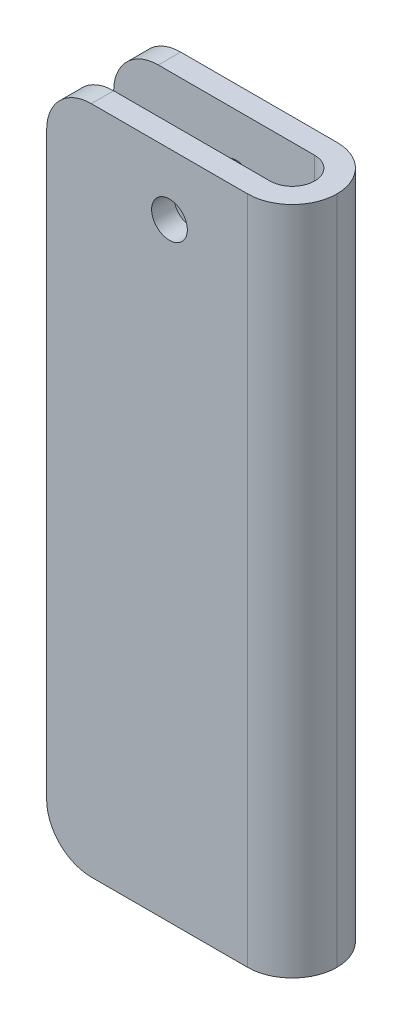
SolidWorks part; units mm, degrees
ref_plane "Plan de face" through (0, 0, 0) normal (0, 0, 1) x (1, 0, 0)
ref_plane "Plan de dessus" through (0, 0, 0) normal (0, 1, 0) x (1, 0, 0)
ref_plane "Plan de droite" through (0, 0, 0) normal (1, 0, 0) x (0, 0, -1)
sketch "Esquisse1" plane through (0, 0, 0) normal (0, 0, 1) x (1, 0, 0)
  line L1 (0, 0) -> (-55, 0)
  line L2 (0, 0) -> (0, 150)
  line L3 (0, 150) -> (-55, 150)
  line L4 (-55, 0) -> (-55, 150)
  dimension "D1" = 55
  dimension "D2" = 150
extrude "Boss.-Extru.1" add sketch "Esquisse1" along normal blind 20
sketch "Esquisse2" plane through (0, 150, 0) normal (0, 1, 0) x (1, 0, 0)
  line L0 (-55, -20) -> (-55, 0) construction
  line L1 (-55, -5) -> (-5, -5)
  line L2 (-55, -5) -> (-55, -15)
  line L3 (-55, -15) -> (-5, -15)
  line L4 (-5, -5) -> (-5, -15)
  line L6 (0, 0) -> (-55, 0) construction
  line L8 (0, -20) -> (0, 0) construction
  point P10 (0, -10)
  dimension "D1" = 10
  dimension "D2" = 5
  dimension "D3" = 5
extrude "Enlèv. mat.-Extru.1" cut sketch "Esquisse2" against normal through all
sketch "Esquisse3" plane through (0, 0, 0) normal (0, 0, -1) x (-1, 0, 0)
  circle A0 centre (27.5, 136.2529) radius 4
extrude "Enlèv. mat.-Extru.2" cut sketch "Esquisse3" against normal blind 20
fillet "Congé1" radius 5 2 edges at (-5, 75, 15) (-5, 75, 5)
fillet "Congé2" radius 10 2 edges at (0, 75, 0) (0, 75, 20)
fillet "Congé3" radius 10 4 edges at (-55, 0, 2.5) (-55, 0, 17.5) (-55, 150, 2.5) (-55, 150, 17.5)
